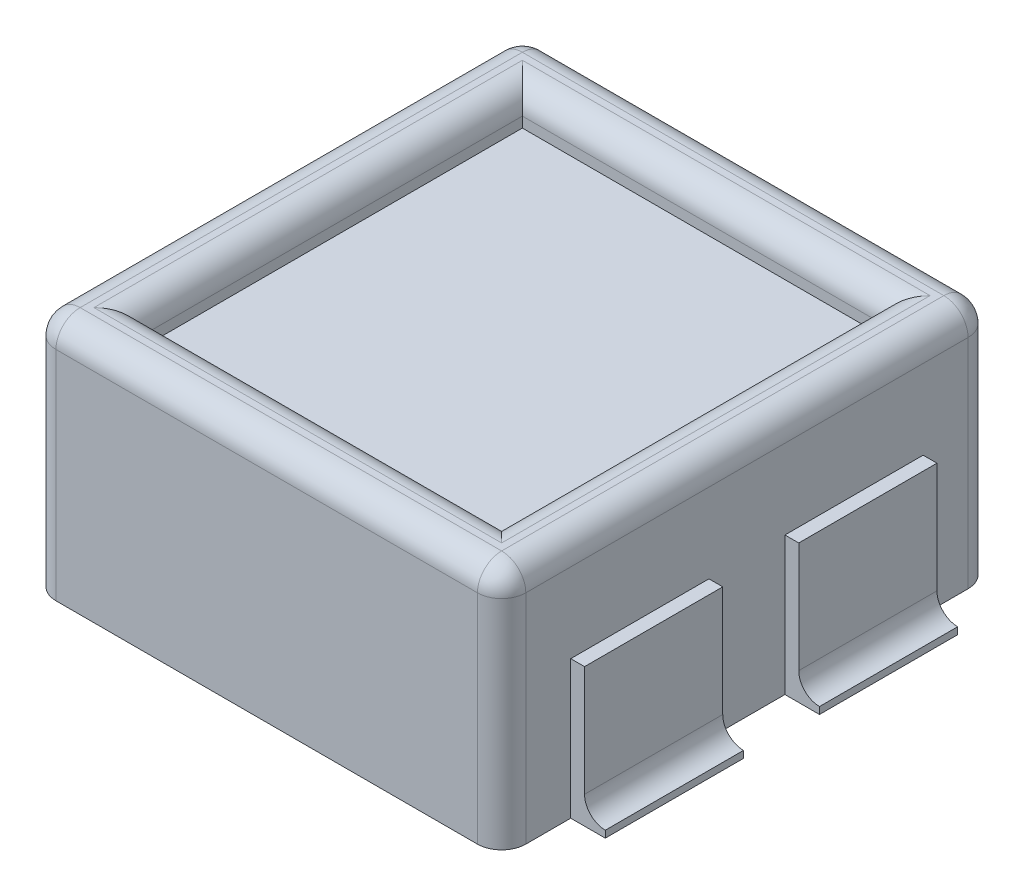
SolidWorks part; units mm, degrees
ref_plane "Front Plane" through (0, 0, 0) normal (0, 0, 1) x (1, 0, 0)
ref_plane "Top Plane" through (0, 0, 0) normal (0, 1, 0) x (1, 0, 0)
ref_plane "Right Plane" through (0, 0, 0) normal (1, 0, 0) x (0, 0, -1)
sketch "Sketch1" plane through (0, 0, 0) normal (0, 1, 0) x (1, 0, 0)
  line L1 (-0.8636, 0.9017) -> (0.8636, 0.9017)
  line L2 (-0.8636, 0.9017) -> (-0.8636, -0.9017)
  line L3 (-0.8636, -0.9017) -> (0.8636, -0.9017)
  line L4 (0.8636, 0.9017) -> (0.8636, -0.9017)
  line L5 (-0.8636, 0.9017) -> (0.8636, -0.9017) construction
  line L6 (-0.8636, -0.9017) -> (0.8636, 0.9017) construction
  point P0 (0, 0)
  dimension "D1" = 1.7272
  dimension "D2" = 1.8034
extrude "Boss-Extrude1" add sketch "Sketch1" along normal blind 0.889
sketch "Sketch2" plane through (0, 0.889, 0) normal (0, 1, 0) x (1, 0, 0)
  line L0 (0.6604, 0) -> (0.8636, 0) construction
  line L1 (-0.6604, 0.6985) -> (0.6604, 0.6985)
  line L2 (-0.6604, 0.6985) -> (-0.6604, -0.6985)
  line L3 (-0.6604, -0.6985) -> (0.6604, -0.6985)
  line L4 (0.6604, 0.6985) -> (0.6604, -0.6985)
  line L5 (-0.6604, 0.6985) -> (0.6604, -0.6985) construction
  line L6 (-0.6604, -0.6985) -> (0.6604, 0.6985) construction
  line L7 (0.8636, -0.9017) -> (0.8636, 0.9017) construction
  line L8 (0, -0.6985) -> (0, -0.9017) construction
  line L9 (-0.8636, -0.9017) -> (0.8636, -0.9017) construction
  point P0 (0, 0)
  point P11 (0.6604, 0)
  point P15 (0, -0.9017)
  dimension "D1" = 0.2032
extrude "Cut-Extrude1" cut sketch "Sketch2" against normal blind 0.127
fillet "Fillet1" radius 0.0889 12 edges at (0, 0.889, 0.9017) (-0.8636, 0.889, 0) (0, 0.889, -0.9017) (0.8636, 0.889, 0) (0, 0.889, -0.6985) (-0.6604, 0.889, 0) (0, 0.889, 0.6985) (0.6604, 0.889, 0) (-0.8636, 0.4445, -0.9017) (0.8636, 0.4445, -0.9017) (0.8636, 0.4445, 0.9017) (-0.8636, 0.4445, 0.9017)
sketch "Sketch3" plane through (0.8636, 0, 0) normal (1, 0, 0) x (0, 0, -1)
  line L0 (0.1397, 0.508) -> (-0.1397, 0.508) construction
  line L1 (-0.6477, 0.508) -> (-0.1397, 0.508)
  line L2 (-0.6477, 0.508) -> (-0.6477, 0)
  line L3 (-0.6477, 0) -> (-0.1397, 0)
  line L4 (-0.1397, 0.508) -> (-0.1397, 0)
  line L5 (0.1397, 0.508) -> (0.6477, 0.508)
  line L6 (0.1397, 0.508) -> (0.1397, 0)
  line L7 (0.1397, 0) -> (0.6477, 0)
  line L8 (0.6477, 0.508) -> (0.6477, 0)
  line L9 (-0.1397, 0.508) -> (-0.1415, 0.5094) construction
  line L10 (-0.8128, 0) -> (0.8128, 0) construction
  point P8 (0, 0.508)
  point P12 (0, 0)
  point P13 (-0.4928, 0.5094)
  dimension "D1" = 0.2794
  dimension "D2" = 0.508
extrude "Boss-Extrude2" add sketch "Sketch3" along normal blind 0.0508
sketch "Sketch4" plane through (0, 0, 0) normal (0, 1, 0) x (1, 0, 0)
  line L0 (0.9144, -0.1397) -> (0.8636, -0.1397) construction
  line L1 (0.9144, -0.6477) -> (0.9906, -0.6477)
  line L2 (0.9144, -0.6477) -> (0.9144, -0.1397)
  line L3 (0.9144, -0.1397) -> (0.9906, -0.1397)
  line L4 (0.9906, -0.6477) -> (0.9906, -0.1397)
  line L5 (0.9144, 0.1397) -> (0.9906, 0.1397)
  line L6 (0.9144, 0.1397) -> (0.9144, 0.6477)
  line L7 (0.9144, 0.6477) -> (0.9906, 0.6477)
  line L8 (0.9906, 0.1397) -> (0.9906, 0.6477)
  line L11 (0.9144, 0.6477) -> (0.8636, 0.6477) construction
  line L12 (0.8636, 0.6477) -> (0.8636, 0.1397) construction
  point P15 (1.1955, 0.5497)
  dimension "D1" = 0.127
extrude "Boss-Extrude3" add sketch "Sketch4" along normal blind 0.0254
fillet "Fillet2" radius 0.0762 2 edges at (0.9144, 0.0254, 0.3937) (0.9144, 0.0254, -0.3937)
mirror "Mirror1" about plane through (0, 0, 0) normal (1, 0, 0) of "Fillet2", "Boss-Extrude3", "Boss-Extrude2"
